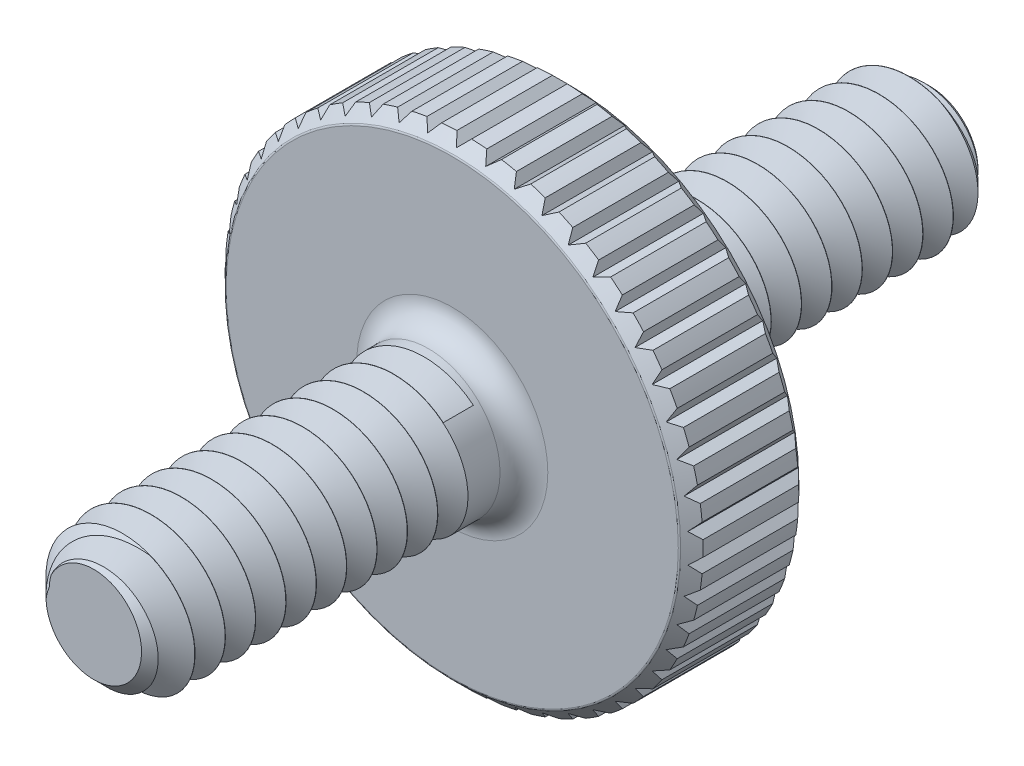
SolidWorks part; units mm, degrees
ref_plane "Спереди" through (0, 0, 0) normal (0, 0, 1) x (1, 0, 0)
ref_plane "Сверху" through (0, 0, 0) normal (0, 1, 0) x (1, 0, 0)
ref_plane "Справа" through (0, 0, 0) normal (1, 0, 0) x (0, 0, -1)
sketch "Эскиз1" plane through (0, 0, 0) normal (0, 0, 1) x (1, 0, 0)
  circle A0 centre (0, 0) radius 10
  dimension "D1" = 20
extrude "Бобышка-Вытянуть1" add sketch "Эскиз1" along normal blind 5
sketch "Эскиз2" plane through (0, 0, 5) normal (0, 0, 1) x (1, 0, 0)
  circle A0 centre (0, 0) radius 3
  dimension "D1" = 6
extrude "Бобышка-Вытянуть2" add sketch "Эскиз2" along normal blind 15
sketch "Эскиз3" plane through (0, 0, 0) normal (0, 0, -1) x (-1, 0, 0)
  circle A0 centre (0, 0) radius 3
  dimension "D1" = 6
extrude "Бобышка-Вытянуть3" add sketch "Эскиз3" along normal blind 15
chamfer "Фаска1" distance 1 angle 45 2 edges at (3, 0, 20) (-3, 0, -15)
chamfer "Фаска2" distance 0.5 angle 45 2 edges at (10, 0, 5) (10, 0, 0)
fillet "Скругление3" radius 1 2 edges at (3, 0, 5) (3, 0, 0)
ref_plane "Плоскость1" through (0, 0, 30) normal (0, 0, 1) x (1, 0, 0)
sketch "Эскиз5" plane through (0, 0, 30) normal (0, 0, 1) x (1, 0, 0)
  circle A0 centre (0, 0) radius 3
  circle A1 centre (0, 0) radius 3 construction
curve "Спираль1" pitch 1.27 height 23.1775 radius 3 centre (0, 0, 30) axis (0, 0, -1) start towards (-0.7071, 0.7071, 0)
sketch "Эскиз7" plane through (0, 0, 0) normal (0, 1, 0) x (1, 0, 0)
  line L0 (1.9088, -20.6781) -> (3, -21.3081)
  line L1 (3, -21.3081) -> (3, -20.0481)
  line L2 (3, -20.0481) -> (1.9088, -20.6781)
  line L3 (3, -19) -> (3, -6) construction
  dimension "D1" = 60
  dimension "D2" = 60
  dimension "D3" = 1.26
sweep "Вырез-По траектории1" cut profiles "Эскиз7" path "Спираль1"
ref_plane "Плоскость4" through (0, 0, 2.5) normal (0, 0, 1) x (1, 0, 0)
ref_plane "Плоскость5" through (0, 0, -17.5) normal (0, 0, -1) x (-1, 0, 0)
sketch "Эскиз12" plane through (0, 0, -17.5) normal (0, 0, -1) x (-1, 0, 0)
  circle A0 centre (0, 0) radius 3
  circle A1 centre (0, 0) radius 3 construction
curve "Спираль3" pitch 1.27 height 15.24 radius 3 centre (0, 0, -17.5) axis (0, 0, 1) start towards (0.7071, 0.7071, 0)
sketch "Эскиз13" plane through (0, 0, 0) normal (0, 1, 0) x (1, 0, 0)
  line L0 (1.9088, 14.8635) -> (3, 15.4935)
  line L1 (3, 15.4935) -> (3, 14.2335)
  line L2 (3, 14.2335) -> (1.9088, 14.8635)
  line L3 (3, 1) -> (3, 14) construction
  dimension "D1" = 60
  dimension "D2" = 60
  dimension "D3" = 1.26
sweep "Вырез-По траектории3" cut profiles "Эскиз13" path "Спираль3"
sketch "Эскиз9" [suppressed] plane through (0, 0, 0) normal (0, 1, 0) x (1, 0, 0)
  line L0 (3.1317, 13.8314) -> (4.5, 14.6214)
  line L1 (4.5, 14.6214) -> (4.5, 13.0414)
  line L2 (4.5, 13.0414) -> (3.1317, 13.8314)
  line L3 (4.5, 1) -> (4.5, 14) construction
  dimension "D1" = 60
  dimension "D2" = 60
  dimension "D3" = 1.58
sketch "Эскиз10" plane through (0, 0, 5) normal (0, 0, 1) x (1, 0, 0)
  line L0 (-0.3136, 10) -> (0, 9.6864)
  line L1 (0, 9.6864) -> (0.3136, 10)
  line L2 (0.3136, 10) -> (-0.3136, 10)
  line L3 (0, 0) -> (0, 12.4341) construction
  line L4 (1.214, 9.61) -> (1.5645, 9.8818)
  line L5 (1.5645, 9.8818) -> (0.9422, 9.9605)
  line L6 (0.9422, 9.9605) -> (1.214, 9.61)
  line L7 (2.4089, 9.3821) -> (2.7907, 9.6078)
  line L8 (2.7907, 9.6078) -> (2.1831, 9.7638)
  line L9 (2.1831, 9.7638) -> (2.4089, 9.3821)
  line L10 (3.5658, 9.0062) -> (3.9728, 9.1823)
  line L11 (3.9728, 9.1823) -> (3.3897, 9.4132)
  line L12 (3.3897, 9.4132) -> (3.5658, 9.0062)
  line L13 (4.6665, 8.4883) -> (5.0924, 8.612)
  line L14 (5.0924, 8.612) -> (4.5427, 8.9141)
  line L15 (4.5427, 8.9141) -> (4.6665, 8.4883)
  line L16 (5.6935, 7.8365) -> (6.1316, 7.9058)
  line L17 (6.1316, 7.9058) -> (5.6241, 8.2745)
  line L18 (5.6241, 8.2745) -> (5.6935, 7.8365)
  line L19 (6.6308, 7.0611) -> (7.0741, 7.075)
  line L20 (7.0741, 7.075) -> (6.6169, 7.5044)
  line L21 (6.6169, 7.5044) -> (6.6308, 7.0611)
  line L22 (7.4635, 6.1743) -> (7.905, 6.1326)
  line L23 (7.905, 6.1326) -> (7.5052, 6.6159)
  line L24 (7.5052, 6.6159) -> (7.4635, 6.1743)
  line L25 (8.1785, 5.1902) -> (8.6113, 5.0935)
  line L26 (8.6113, 5.0935) -> (8.2752, 5.6231)
  line L27 (8.2752, 5.6231) -> (8.1785, 5.1902)
  line L28 (8.7645, 4.1243) -> (9.1818, 3.974)
  line L29 (9.1818, 3.974) -> (8.9147, 4.5416)
  line L30 (8.9147, 4.5416) -> (8.7645, 4.1243)
  line L31 (9.2123, 2.9933) -> (9.6075, 2.7919)
  line L32 (9.6075, 2.7919) -> (9.4137, 3.3884)
  line L33 (9.4137, 3.3884) -> (9.2123, 2.9933)
  line L34 (9.5148, 1.815) -> (9.8816, 1.5658)
  line L35 (9.8816, 1.5658) -> (9.7641, 2.1819)
  line L36 (9.7641, 2.1819) -> (9.5148, 1.815)
  line L37 (9.6673, 0.6082) -> (10, 0.3149)
  line L38 (10, 0.3149) -> (9.9606, 0.9409)
  line L39 (9.9606, 0.9409) -> (9.6673, 0.6082)
  line L40 (9.6673, -0.6082) -> (9.9606, -0.9409)
  line L41 (9.9606, -0.9409) -> (10, -0.3149)
  line L42 (10, -0.3149) -> (9.6673, -0.6082)
  line L43 (9.5148, -1.815) -> (9.7641, -2.1819)
  line L44 (9.7641, -2.1819) -> (9.8816, -1.5658)
  line L45 (9.8816, -1.5658) -> (9.5148, -1.815)
  line L46 (9.2123, -2.9933) -> (9.4137, -3.3884)
  line L47 (9.4137, -3.3884) -> (9.6075, -2.7919)
  line L48 (9.6075, -2.7919) -> (9.2123, -2.9933)
  line L49 (8.7645, -4.1243) -> (8.9147, -4.5416)
  line L50 (8.9147, -4.5416) -> (9.1818, -3.974)
  line L51 (9.1818, -3.974) -> (8.7645, -4.1243)
  line L52 (8.1785, -5.1902) -> (8.2752, -5.6231)
  line L53 (8.2752, -5.6231) -> (8.6113, -5.0935)
  line L54 (8.6113, -5.0935) -> (8.1785, -5.1902)
  line L55 (7.4635, -6.1743) -> (7.5052, -6.6159)
  line L56 (7.5052, -6.6159) -> (7.905, -6.1326)
  line L57 (7.905, -6.1326) -> (7.4635, -6.1743)
  line L58 (6.6308, -7.0611) -> (6.6169, -7.5044)
  line L59 (6.6169, -7.5044) -> (7.0741, -7.075)
  line L60 (7.0741, -7.075) -> (6.6308, -7.0611)
  line L61 (5.6935, -7.8365) -> (5.6241, -8.2745)
  line L62 (5.6241, -8.2745) -> (6.1316, -7.9058)
  line L63 (6.1316, -7.9058) -> (5.6935, -7.8365)
  line L64 (4.6665, -8.4883) -> (4.5427, -8.9141)
  line L65 (4.5427, -8.9141) -> (5.0924, -8.612)
  line L66 (5.0924, -8.612) -> (4.6665, -8.4883)
  line L67 (3.5658, -9.0062) -> (3.3897, -9.4132)
  line L68 (3.3897, -9.4132) -> (3.9728, -9.1823)
  line L69 (3.9728, -9.1823) -> (3.5658, -9.0062)
  line L70 (2.4089, -9.3821) -> (2.1831, -9.7638)
  line L71 (2.1831, -9.7638) -> (2.7907, -9.6078)
  line L72 (2.7907, -9.6078) -> (2.4089, -9.3821)
  line L73 (1.214, -9.61) -> (0.9422, -9.9605)
  line L74 (0.9422, -9.9605) -> (1.5645, -9.8818)
  line L75 (1.5645, -9.8818) -> (1.214, -9.61)
  line L76 (0, -9.6864) -> (-0.3136, -10)
  line L77 (-0.3136, -10) -> (0.3136, -10)
  line L78 (0.3136, -10) -> (0, -9.6864)
  line L79 (-1.214, -9.61) -> (-1.5645, -9.8818)
  line L80 (-1.5645, -9.8818) -> (-0.9422, -9.9605)
  line L81 (-0.9422, -9.9605) -> (-1.214, -9.61)
  line L82 (-2.4089, -9.3821) -> (-2.7907, -9.6078)
  line L83 (-2.7907, -9.6078) -> (-2.1831, -9.7638)
  line L84 (-2.1831, -9.7638) -> (-2.4089, -9.3821)
  line L85 (-3.5658, -9.0062) -> (-3.9728, -9.1823)
  line L86 (-3.9728, -9.1823) -> (-3.3897, -9.4132)
  line L87 (-3.3897, -9.4132) -> (-3.5658, -9.0062)
  line L88 (-4.6665, -8.4883) -> (-5.0924, -8.612)
  line L89 (-5.0924, -8.612) -> (-4.5427, -8.9141)
  line L90 (-4.5427, -8.9141) -> (-4.6665, -8.4883)
  line L91 (-5.6935, -7.8365) -> (-6.1316, -7.9058)
  line L92 (-6.1316, -7.9058) -> (-5.6241, -8.2745)
  line L93 (-5.6241, -8.2745) -> (-5.6935, -7.8365)
  line L94 (-6.6308, -7.0611) -> (-7.0741, -7.075)
  line L95 (-7.0741, -7.075) -> (-6.6169, -7.5044)
  line L96 (-6.6169, -7.5044) -> (-6.6308, -7.0611)
  line L97 (-7.4635, -6.1743) -> (-7.905, -6.1326)
  line L98 (-7.905, -6.1326) -> (-7.5052, -6.6159)
  line L99 (-7.5052, -6.6159) -> (-7.4635, -6.1743)
  line L100 (-8.1785, -5.1902) -> (-8.6113, -5.0935)
  line L101 (-8.6113, -5.0935) -> (-8.2752, -5.6231)
  line L102 (-8.2752, -5.6231) -> (-8.1785, -5.1902)
  line L103 (-8.7645, -4.1243) -> (-9.1818, -3.974)
  line L104 (-9.1818, -3.974) -> (-8.9147, -4.5416)
  line L105 (-8.9147, -4.5416) -> (-8.7645, -4.1243)
  line L106 (-9.2123, -2.9933) -> (-9.6075, -2.7919)
  line L107 (-9.6075, -2.7919) -> (-9.4137, -3.3884)
  line L108 (-9.4137, -3.3884) -> (-9.2123, -2.9933)
  line L109 (-9.5148, -1.815) -> (-9.8816, -1.5658)
  line L110 (-9.8816, -1.5658) -> (-9.7641, -2.1819)
  line L111 (-9.7641, -2.1819) -> (-9.5148, -1.815)
  line L112 (-9.6673, -0.6082) -> (-10, -0.3149)
  line L113 (-10, -0.3149) -> (-9.9606, -0.9409)
  line L114 (-9.9606, -0.9409) -> (-9.6673, -0.6082)
  line L115 (-9.6673, 0.6082) -> (-9.9606, 0.9409)
  line L116 (-9.9606, 0.9409) -> (-10, 0.3149)
  line L117 (-10, 0.3149) -> (-9.6673, 0.6082)
  line L118 (-9.5148, 1.815) -> (-9.7641, 2.1819)
  line L119 (-9.7641, 2.1819) -> (-9.8816, 1.5658)
  line L120 (-9.8816, 1.5658) -> (-9.5148, 1.815)
  line L121 (-9.2123, 2.9933) -> (-9.4137, 3.3884)
  line L122 (-9.4137, 3.3884) -> (-9.6075, 2.7919)
  line L123 (-9.6075, 2.7919) -> (-9.2123, 2.9933)
  line L124 (-8.7645, 4.1243) -> (-8.9147, 4.5416)
  line L125 (-8.9147, 4.5416) -> (-9.1818, 3.974)
  line L126 (-9.1818, 3.974) -> (-8.7645, 4.1243)
  line L127 (-8.1785, 5.1902) -> (-8.2752, 5.6231)
  line L128 (-8.2752, 5.6231) -> (-8.6113, 5.0935)
  line L129 (-8.6113, 5.0935) -> (-8.1785, 5.1902)
  line L130 (-7.4635, 6.1743) -> (-7.5052, 6.6159)
  line L131 (-7.5052, 6.6159) -> (-7.905, 6.1326)
  line L132 (-7.905, 6.1326) -> (-7.4635, 6.1743)
  line L133 (-6.6308, 7.0611) -> (-6.6169, 7.5044)
  line L134 (-6.6169, 7.5044) -> (-7.0741, 7.075)
  line L135 (-7.0741, 7.075) -> (-6.6308, 7.0611)
  line L136 (-5.6935, 7.8365) -> (-5.6241, 8.2745)
  line L137 (-5.6241, 8.2745) -> (-6.1316, 7.9058)
  line L138 (-6.1316, 7.9058) -> (-5.6935, 7.8365)
  line L139 (-4.6665, 8.4883) -> (-4.5427, 8.9141)
  line L140 (-4.5427, 8.9141) -> (-5.0924, 8.612)
  line L141 (-5.0924, 8.612) -> (-4.6665, 8.4883)
  line L142 (-3.5658, 9.0062) -> (-3.3897, 9.4132)
  line L143 (-3.3897, 9.4132) -> (-3.9728, 9.1823)
  line L144 (-3.9728, 9.1823) -> (-3.5658, 9.0062)
  line L145 (-2.4089, 9.3821) -> (-2.1831, 9.7638)
  line L146 (-2.1831, 9.7638) -> (-2.7907, 9.6078)
  line L147 (-2.7907, 9.6078) -> (-2.4089, 9.3821)
  line L148 (-1.214, 9.61) -> (-0.9422, 9.9605)
  line L149 (-0.9422, 9.9605) -> (-1.5645, 9.8818)
  line L150 (-1.5645, 9.8818) -> (-1.214, 9.61)
  circle A0 centre (0, 0) radius 10 construction
  point P99 (0, 0)
  dimension "D1" = 90
  dimension "D2" = 45
  dimension "D3" = 50
extrude "Вырез-Вытянуть1" cut sketch "Эскиз10" against normal through all
fillet "Скругление1" radius 0.1 2 edges at (9.5, 0, 0) (9.5, 0, 5)
